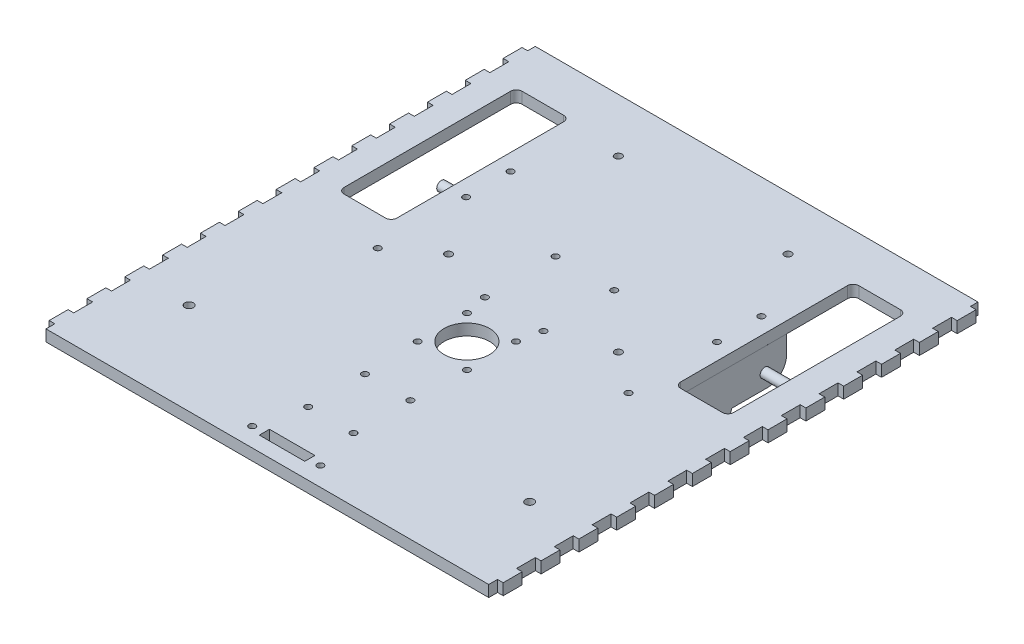
SolidWorks part; units mm, degrees
ref_plane "Front Plane" through (0, 0, 0) normal (0, 0, 1) x (1, 0, 0)
ref_plane "Top Plane" through (0, 0, 0) normal (0, 1, 0) x (1, 0, 0)
ref_plane "Right Plane" through (0, 0, 0) normal (1, 0, 0) x (0, 0, -1)
sketch "Sketch2" plane through (0, 0, 0) normal (0, 1, 0) x (1, 0, 0)
  line L7 (-186.2662, -88.2141) -> (47.7338, -88.2141)
  line L48 (-172.2662, 146.3841) -> (-144.2662, 146.3841)
  line L49 (-172.2662, 146.3841) -> (-172.2662, 52.2603)
  line L50 (-172.2662, 52.2603) -> (-144.2662, 52.2603)
  line L51 (-144.2662, 146.3841) -> (-144.2662, 52.2603)
  line L72 (47.7338, 170.3841) -> (-186.2662, 170.3841)
  line L75 (-69.2662, 154.3841) -> (-69.2662, -88.2141) construction
  line L76 (47.7338, -88.2141) -> (47.7338, 170.3841)
  line L77 (5.7338, 146.3841) -> (5.7338, 52.2603)
  line L78 (33.7338, 52.2603) -> (5.7338, 52.2603)
  line L79 (-186.2662, -88.2141) -> (-186.2662, 170.3841)
  line L80 (33.7338, 146.3841) -> (33.7338, 52.2603)
  line L81 (33.7338, 146.3841) -> (5.7338, 146.3841)
  point P2 (-158.2662, 146.3841)
  dimension "D6" = 117
  dimension "D9" = 28
  dimension "D3" = 14
  dimension "D1" = 24
extrude "Boss-Extrude1" add sketch "Sketch2" along normal blind 6
ref_plane "Plane3" through (-69.2662, 0, 0) normal (-1, 0, 0) x (0, 0, 1)
sketch "Sketch4" plane through (0, 0, 0) normal (0, -1, 0) x (1, 0, 0)
  line L5 (-186.2662, 15.9553) -> (47.7338, 15.9553) construction
  line L6 (-186.2662, -170.3841) -> (-186.2662, 88.2141) construction
  line L7 (47.7338, 88.2141) -> (47.7338, -170.3841) construction
  point P6 (-69.2662, 15.9553)
  line B0 (-144.2673, -111.2297) -> (-144.2673, -31.6718)
  line B1 (-144.2673, -111.2297) -> (-131.4267, -111.2297)
  line B2 (-144.2673, -31.6718) -> (-131.4299, -31.6718)
  line B3 (-80.7662, -37.9313) -> (-80.7662, -84.2325)
  line B4 (-80.7662, -37.9313) -> (-89.1807, -37.9313)
  line B5 (-80.7662, -84.2325) -> (-89.1807, -84.2325)
  line B6 (-126.4299, -36.6718) -> (-126.4299, -60.4336)
  line B7 (-126.4299, -60.4336) -> (-89.1807, -60.4336)
  line B8 (-89.1807, -60.4336) -> (-89.1807, -37.9313)
  line B9 (-89.1807, -84.2325) -> (-89.1807, -67.1203)
  line B10 (-89.1807, -67.1203) -> (-126.4267, -67.1203)
  line B11 (-126.4267, -67.1203) -> (-126.4267, -106.2297)
  arc B12 (-131.4299, -31.6718) -> (-126.4299, -36.6718) centre (-131.4299, -36.6718) cw
  arc B13 (-131.4267, -111.2297) -> (-126.4267, -106.2297) centre (-131.4267, -106.2297) ccw
  dimension "D1" = 11.5
sketch_block_instance "Block1-1"
sketch_block "Block1" parameters "D1"=5
extrude "Boss-Extrude3" add sketch "Sketch4" along normal blind 1.6129 separate body
sketch "Sketch6" plane through (-144.2673, 113.8349, 0) normal (1, 0, 0) x (0, -1, 0)
  line L1 (113.8349, 31.6718) -> (113.8349, 111.2297)
  line L7 (123.4041, 111.2297) -> (113.8349, 111.2297)
  line L8 (113.8349, 52.2603) -> (113.8349, 146.3841) construction
  line L10 (115.4478, 111.2297) -> (113.8349, 111.2297) construction
  line L11 (133.4041, 101.2297) -> (133.4041, 82.2567)
  line L13 (132.4365, 35.6062) -> (115.4478, 31.6718)
  line L14 (115.4478, 31.6718) -> (113.8349, 31.6718)
  circle A2 centre (133.4041, 71.8386) radius 1.27
  circle A4 centre (133.4041, 49.6644) radius 3
  circle A5 centre (125.8349, 99.7882) radius 2.55
  circle A6 centre (123.1933, 49.6644) radius 1.27
  circle A8 centre (143.6149, 49.6644) radius 1.27
  arc A10 (133.4041, 82.2567) -> (132.4365, 35.6062) centre (127.5185, 59.0435) cw
  arc A11 (133.4041, 101.2297) -> (123.4041, 111.2297) centre (123.4041, 101.2297) ccw
  line M25 (113.8349, 31.6718) -> (113.8349, 111.2297)
  line M26 (113.8349, 111.2297) -> (115.4478, 111.2297)
  line M27 (115.4478, 111.2297) -> (115.4478, 31.6718)
  line M28 (115.4478, 31.6718) -> (113.8349, 31.6718)
  dimension "D1" = 5.1
  dimension "D4" = 6
  dimension "D5" = 10
  dimension "D2" = 12
extrude "Boss-Extrude4" add sketch "Sketch6" along normal blind 1.6129 contours M28 M25 M26 M27 | M27 | A6 A2 A4 A8 region at (-144.2673, -0.8064, -71.4508) region at (-144.2673, -15.5641, -67.9069)
sketch "Sketch13" plane through (0, 6, 0) normal (0, 1, 0) x (1, 0, 0)
  line L0 (50.7338, 166.3841) -> (47.7338, 166.3841)
  line L1 (47.7338, 166.3841) -> (47.7338, 156.3841)
  line L2 (47.7338, 156.3841) -> (50.7338, 156.3841)
  line L3 (47.7338, -88.2141) -> (47.7338, 170.3841) construction
  line L4 (50.7338, 156.3841) -> (50.7338, 166.3841)
  line L5 (-69.2662, -1088.2141) -> (-69.2662, 48911.7859) construction
  line L6 (47.7338, 170.3841) -> (-186.2662, 170.3841) construction
  line L7 (50.7338, 146.3889) -> (47.7338, 146.3889)
  line L8 (47.7338, 146.3889) -> (47.7338, 136.3889)
  line L9 (47.7338, 136.3889) -> (50.7338, 136.3889)
  line L10 (50.7338, 136.3889) -> (50.7338, 146.3889)
  line L11 (50.7338, 126.3938) -> (47.7338, 126.3938)
  line L12 (47.7338, 126.3938) -> (47.7338, 116.3938)
  line L13 (47.7338, 116.3938) -> (50.7338, 116.3938)
  line L14 (50.7338, 116.3938) -> (50.7338, 126.3938)
  line L15 (50.7338, 106.3986) -> (47.7338, 106.3986)
  line L16 (47.7338, 106.3986) -> (47.7338, 96.3986)
  line L17 (47.7338, 96.3986) -> (50.7338, 96.3986)
  line L18 (50.7338, 96.3986) -> (50.7338, 106.3986)
  line L19 (50.7338, 86.4035) -> (47.7338, 86.4035)
  line L20 (47.7338, 86.4035) -> (47.7338, 76.4035)
  line L21 (47.7338, 76.4035) -> (50.7338, 76.4035)
  line L22 (50.7338, 76.4035) -> (50.7338, 86.4035)
  line L23 (50.7338, 66.4083) -> (47.7338, 66.4083)
  line L24 (47.7338, 66.4083) -> (47.7338, 56.4083)
  line L25 (47.7338, 56.4083) -> (50.7338, 56.4083)
  line L26 (50.7338, 56.4083) -> (50.7338, 66.4083)
  line L27 (50.7338, 46.4131) -> (47.7338, 46.4131)
  line L28 (47.7338, 46.4131) -> (47.7338, 36.4131)
  line L29 (47.7338, 36.4131) -> (50.7338, 36.4131)
  line L30 (50.7338, 36.4131) -> (50.7338, 46.4131)
  line L31 (50.7338, 26.418) -> (47.7338, 26.418)
  line L32 (47.7338, 26.418) -> (47.7338, 16.418)
  line L33 (47.7338, 16.418) -> (50.7338, 16.418)
  line L34 (50.7338, 16.418) -> (50.7338, 26.418)
  line L35 (50.7338, 6.4228) -> (47.7338, 6.4228)
  line L36 (47.7338, 6.4228) -> (47.7338, -3.5772)
  line L37 (47.7338, -3.5772) -> (50.7338, -3.5772)
  line L38 (50.7338, -3.5772) -> (50.7338, 6.4228)
  line L39 (50.7338, -13.5723) -> (47.7338, -13.5723)
  line L40 (47.7338, -13.5723) -> (47.7338, -23.5723)
  line L41 (47.7338, -23.5723) -> (50.7338, -23.5723)
  line L42 (50.7338, -23.5723) -> (50.7338, -13.5723)
  line L43 (50.7338, -33.5675) -> (47.7338, -33.5675)
  line L44 (47.7338, -33.5675) -> (47.7338, -43.5675)
  line L45 (47.7338, -43.5675) -> (50.7338, -43.5675)
  line L46 (50.7338, -43.5675) -> (50.7338, -33.5675)
  line L47 (50.7338, -53.5627) -> (47.7338, -53.5627)
  line L48 (47.7338, -53.5627) -> (47.7338, -63.5627)
  line L49 (47.7338, -63.5627) -> (50.7338, -63.5627)
  line L50 (50.7338, -63.5627) -> (50.7338, -53.5627)
  line L99 (50.7338, -73.5578) -> (47.7338, -73.5578)
  line L100 (47.7338, -73.5578) -> (47.7338, -83.5578)
  line L101 (47.7338, -83.5578) -> (50.7338, -83.5578)
  line L102 (50.7338, -83.5578) -> (50.7338, -73.5578)
  line L103 (-186.2662, -88.2141) -> (47.7338, -88.2141) construction
  line L104 (-189.2662, -83.5578) -> (-189.2662, -73.5578)
  line L105 (-186.2662, -83.5578) -> (-189.2662, -83.5578)
  line L106 (-186.2662, -73.5578) -> (-186.2662, -83.5578)
  line L107 (-189.2662, -73.5578) -> (-186.2662, -73.5578)
  line L108 (-189.2662, -63.5627) -> (-189.2662, -53.5627)
  line L109 (-186.2662, -63.5627) -> (-189.2662, -63.5627)
  line L110 (-186.2662, -53.5627) -> (-186.2662, -63.5627)
  line L111 (-189.2662, -53.5627) -> (-186.2662, -53.5627)
  line L112 (-189.2662, -43.5675) -> (-189.2662, -33.5675)
  line L113 (-186.2662, -43.5675) -> (-189.2662, -43.5675)
  line L114 (-186.2662, -33.5675) -> (-186.2662, -43.5675)
  line L115 (-189.2662, -33.5675) -> (-186.2662, -33.5675)
  line L116 (-189.2662, -23.5723) -> (-189.2662, -13.5723)
  line L117 (-186.2662, -23.5723) -> (-189.2662, -23.5723)
  line L118 (-186.2662, -13.5723) -> (-186.2662, -23.5723)
  line L119 (-189.2662, -13.5723) -> (-186.2662, -13.5723)
  line L120 (-189.2662, -3.5772) -> (-189.2662, 6.4228)
  line L121 (-186.2662, -3.5772) -> (-189.2662, -3.5772)
  line L122 (-186.2662, 6.4228) -> (-186.2662, -3.5772)
  line L123 (-189.2662, 6.4228) -> (-186.2662, 6.4228)
  line L124 (-189.2662, 16.418) -> (-189.2662, 26.418)
  line L125 (-186.2662, 16.418) -> (-189.2662, 16.418)
  line L126 (-186.2662, 26.418) -> (-186.2662, 16.418)
  line L127 (-189.2662, 26.418) -> (-186.2662, 26.418)
  line L128 (-189.2662, 36.4131) -> (-189.2662, 46.4131)
  line L129 (-186.2662, 36.4131) -> (-189.2662, 36.4131)
  line L130 (-186.2662, 46.4131) -> (-186.2662, 36.4131)
  line L131 (-189.2662, 46.4131) -> (-186.2662, 46.4131)
  line L132 (-189.2662, 56.4083) -> (-189.2662, 66.4083)
  line L133 (-186.2662, 56.4083) -> (-189.2662, 56.4083)
  line L134 (-186.2662, 66.4083) -> (-186.2662, 56.4083)
  line L135 (-189.2662, 66.4083) -> (-186.2662, 66.4083)
  line L136 (-189.2662, 76.4035) -> (-189.2662, 86.4035)
  line L137 (-186.2662, 76.4035) -> (-189.2662, 76.4035)
  line L138 (-186.2662, 86.4035) -> (-186.2662, 76.4035)
  line L139 (-189.2662, 86.4035) -> (-186.2662, 86.4035)
  line L140 (-189.2662, 96.3986) -> (-189.2662, 106.3986)
  line L141 (-186.2662, 96.3986) -> (-189.2662, 96.3986)
  line L142 (-186.2662, 106.3986) -> (-186.2662, 96.3986)
  line L143 (-189.2662, 106.3986) -> (-186.2662, 106.3986)
  line L144 (-189.2662, 116.3938) -> (-189.2662, 126.3938)
  line L145 (-186.2662, 116.3938) -> (-189.2662, 116.3938)
  line L146 (-186.2662, 126.3938) -> (-186.2662, 116.3938)
  line L147 (-189.2662, 126.3938) -> (-186.2662, 126.3938)
  line L148 (-189.2662, 136.3889) -> (-189.2662, 146.3889)
  line L149 (-186.2662, 136.3889) -> (-189.2662, 136.3889)
  line L150 (-186.2662, 146.3889) -> (-186.2662, 136.3889)
  line L151 (-189.2662, 146.3889) -> (-186.2662, 146.3889)
  line L152 (-189.2662, 156.3841) -> (-189.2662, 166.3841)
  line L153 (-186.2662, 156.3841) -> (-189.2662, 156.3841)
  line L154 (-186.2662, 166.3841) -> (-186.2662, 156.3841)
  line L155 (-189.2662, 166.3841) -> (-186.2662, 166.3841)
  point P13 (-69.2662, -88.2141)
  dimension "D1" = 10
  dimension "D2" = 3
  dimension "D4" = 4
  dimension "D3" = 13
extrude "Boss-Extrude7" add sketch "Sketch13" against normal blind 6
sketch "Sketch7" plane through (0, 0, 0) normal (0, -1, 0) x (1, 0, 0)
  line L0 (-186.2662, 88.2141) -> (47.7338, 88.2141) construction
  line L1 (-69.2662, -5.2299) -> (-69.2662, -29.2299)
  line L48 (-69.2662, -1159.7859) -> (-69.2662, 48840.2141) construction
  line L49 (47.7338, -170.3841) -> (-186.2662, -170.3841) construction
  line L50 (-69.2662, 80.4578) -> (-69.2662, 75.1009)
  line L51 (-69.2662, 80.4578) -> (-81.2662, 80.4578)
  line L52 (-69.2662, 75.1009) -> (-81.2662, 75.1009)
  line L53 (-81.2662, 80.4578) -> (-81.2662, 75.1009)
  circle A0 centre (-135.5463, -83.1098) radius 1.7
  circle A1 centre (-135.5463, -36.3977) radius 1.7
  circle A2 centre (-84.7521, -42.2194) radius 1.7
  circle A3 centre (-84.7521, -79.6224) radius 1.7
  circle A4 centre (-135.5463, -106.6172) radius 1.7
  circle A5 centre (-114.1162, -52.4299) radius 1.9
  circle A6 centre (-114.1162, -142.1299) radius 1.9
  circle A7 centre (-159.2662, 39.5701) radius 2.25
  circle A8 centre (-82.2662, -4.2299) radius 1.7
  circle A9 centre (-82.2662, -30.2299) radius 1.7
  arc A11 (-69.2662, -5.2299) -> (-69.2662, -29.2299) centre (-69.2662, -17.2299) ccw
  circle A12 centre (-87.2662, 78.2141) radius 1.7
  circle A13 centre (-81.2662, 24.6349) radius 1.7
  circle A14 centre (-81.2662, 54.6349) radius 1.7
  point P38 (-69.2662, -170.3841)
  dimension "D3" = 3.4
  dimension "D4" = 3.4
  dimension "D5" = 3.4
  dimension "D6" = 3.4
  dimension "D1" = 3.4
  dimension "D2" = 3.8
  dimension "D8" = 3.8
  dimension "D9" = 4.5
  dimension "D12" = 3.4
  dimension "D13" = 3.4
  dimension "D14" = 12
  dimension "D20" = 3.4
  dimension "D23" = 3.4
  dimension "D24" = 3.4
  dimension "D22" = 10
  dimension "D25" = 30
  dimension "D15" = 13
  dimension "D19" = 12
  dimension "D21" = 18
  dimension "D11" = 89.7
  dimension "D17" = 13
  dimension "D18" = 26
  dimension "D7" = 92
  dimension "D16" = 44.85
  dimension "D10" = 90
  dimension "D28" = 35.2
  dimension "D26" = 12
  dimension "D27" = 66.2801
  dimension "D29" = 15.4859
extrude "Cut-Extrude1" cut sketch "Sketch7" against normal blind 10 and the other way blind 10
mirror "Mirror1" about plane through (-69.2662, 0, 0) normal (-1, 0, 0) of bodies 157 158 103
mirror "Mirror2" about plane through (-69.2662, 0, 0) normal (-1, 0, 0) of "Cut-Extrude1"
sketch "Sketch9" plane through (-144.2662, 0, 0) normal (1, 0, 0) x (0, 0, -1)
  circle A0 centre (99.7882, -12) radius 2.5
extrude "Boss-Extrude6" add sketch "Sketch9" along normal blind 169 and the other way blind 21 separate body
fillet "Fillet1" radius 3 8 edges at (-144.2662, 3, -52.2603) (-172.2662, 3, -146.3841) (-172.2662, 3, -52.2603) (-144.2662, 3, -146.3841) (33.7338, 3, -146.3841) (5.7338, 3, -146.3841) (33.7338, 3, -52.2603) (5.7338, 3, -52.2603)
equation "\"hardboard_width\"= 3"
equation "\"D1@Boss-Extrude1\"=\"hardboard_width\""
equation "\"steel_24g_thickness\"= 0.5"
equation "\"m3_clearance_hole\"= 3.4"
equation "\"D3@Sketch7\"=\"m3_clearance_hole\""
equation "\"D4@Sketch7\"=\"m3_clearance_hole\""
equation "\"D5@Sketch7\"=\"m3_clearance_hole\""
equation "\"D6@Sketch7\"=\"m3_clearance_hole\""
equation "\"steel_16g_thickness\"=1.6129"
equation "\"D1@Boss-Extrude3\"=\"steel_16g_thickness\""
equation "\"D1@Boss-Extrude4\"=\"steel_16g_thickness\""
equation "\"D1@Sketch7\"=\"m3_clearance_hole\""
equation "\"D12@Sketch7\"=\"m3_clearance_hole\""
equation "\"D20@Sketch7\"=\"m3_clearance_hole\""
equation "\"D23@Sketch7\"=\"m3_clearance_hole\""
equation "\"D24@Sketch7\"=\"m3_clearance_hole\""
equation "\"D13@Sketch7\"=\"m3_clearance_hole\""
equation "\"D28@Sketch7\"=80.05-44.85"
equation "\"D2@Sketch13\"=\"hardboard_width\""
equation "\"robot_width\"= 234"
equation "\"D6@Sketch2\"=\"robot_width\"/2"
